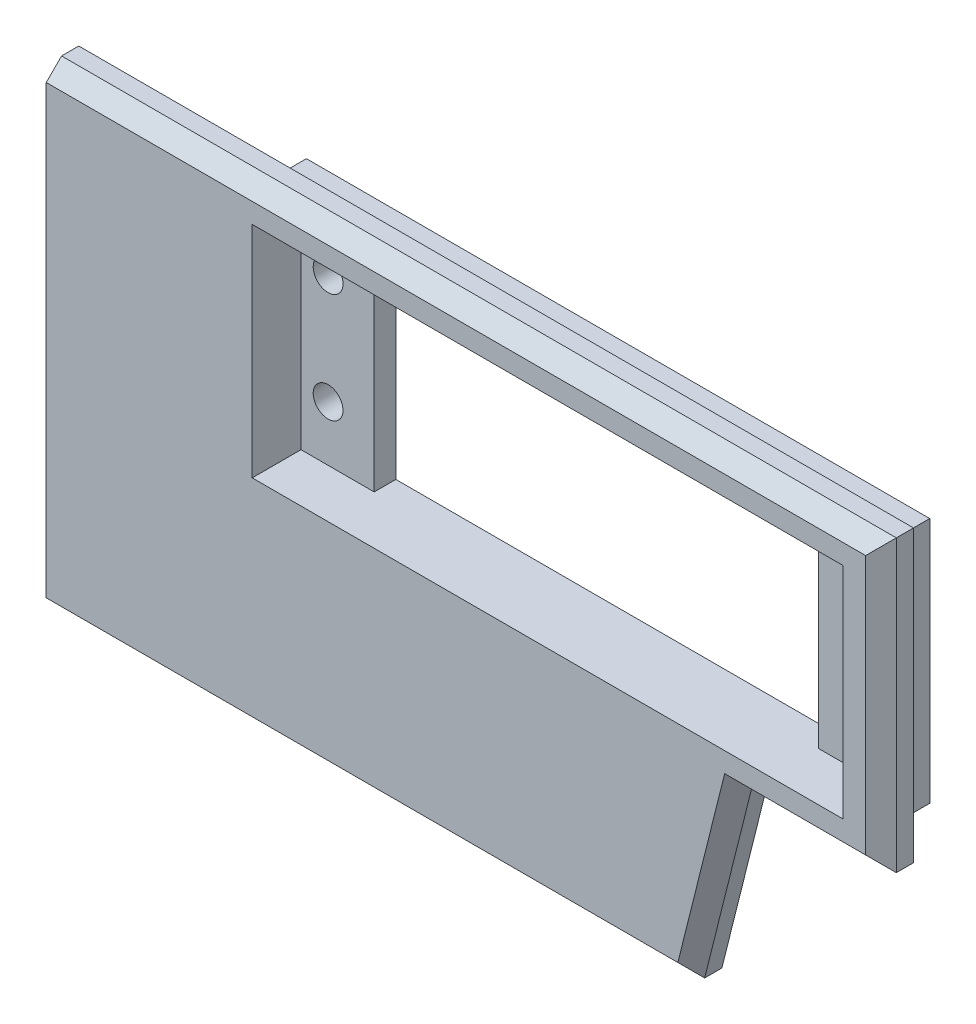
SolidWorks part; units mm, degrees
ref_plane "Front Plane" through (0, 0, 0) normal (0, 0, 1) x (1, 0, 0)
ref_plane "Top Plane" through (0, 0, 0) normal (0, 1, 0) x (1, 0, 0)
ref_plane "Right Plane" through (0, 0, 0) normal (1, 0, 0) x (0, 0, -1)
sketch "Sketch4" plane through (0, 0, 0) normal (0, 0, 1) x (1, 0, 0)
  line L0 (22.8744, -2.75) -> (36.233, -2.75)
  line L1 (36.233, -2.75) -> (36.233, 24)
  line L2 (36.233, 24) -> (-40.767, 24)
  line L3 (-40.767, 24) -> (-40.767, -20)
  line L4 (-40.767, -20) -> (18.556, -20)
  line L5 (18.556, -20) -> (22.8744, -2.75)
  line L10 (-42.767, -20) -> (18.556, -20) construction
  line L11 (-40.767, 18) -> (-40.767, -14.04) construction
  line L12 (36.233, -2.75) -> (36.233, 24) construction
  line L13 (36.233, 24) -> (-52.767, 24) construction
  line L14 (22.8744, -2.75) -> (36.233, -2.75) construction
extrude "Boss-Extrude1" add sketch "Sketch4" along normal blind 3
sketch "Sketch5" plane through (36.233, 0, 0) normal (1, 0, 0) x (0, 0, -1)
  line L0 (-1.5858, 24) -> (-3, 22.5858)
  line L1 (-3, 24) -> (0, 24) construction
  line L2 (-3, -2.75) -> (-3, 24) construction
  line L3 (-3, 22.5858) -> (-3, 24)
  line L4 (-3, 24) -> (-1.5858, 24)
  line L5 (-3, -18.5858) -> (-1.5858, -20)
  line L6 (-3, -20) -> (-3, -2.75) construction
  line L7 (-3, -20) -> (0, -20) construction
  line L8 (-1.5858, -20) -> (-3, -20)
  line L9 (-3, -20) -> (-3, -18.5858)
  line L10 (-3, 10.625) -> (0, 10.625) construction
  line L11 (0, -2.75) -> (0, 24) construction
  line L12 (-3, -1.3358) -> (-3, -2.75)
  line L13 (-3, -2.75) -> (-1.5858, -2.75)
  line L14 (-1.5858, -2.75) -> (-3, -1.3358)
  line M8 (0, 24) -> (-3, 24)
  line M9 (-3, 24) -> (-3, -2.75)
  line M10 (-3, -2.75) -> (0, -2.75)
  dimension "D1" = 2
  dimension "D2" = 2
extrude "Cut-Extrude1" cut sketch "Sketch5" against normal up to next contours L0 M8 M9 | L5 L8 L9 region at (36.233, 23.5286, 2.5286)
extrude "Cut-Extrude2" cut sketch "Sketch5<4>" against normal up to surface (13.0046 mm away) contours L14 M10 M9 region at (36.233, -2.2786, 2.5286) up to face at (20.3541, -12.8172, 1.5172)
sketch "Sketch5<4>" plane through (36.233, 0, 0) normal (1, 0, 0) x (0, 0, -1) same geometry as "Sketch5"
sketch "Sketch7" plane through (0, -2.75, 0) normal (0, -1, 0) x (1, 0, 0)
  line L0 (36.233, 1.5858) -> (34.8188, 3)
  line L4 (34.8188, 3) -> (36.233, 3)
  line L5 (36.233, 3) -> (36.233, 1.5858)
  line L6 (23.2284, 3) -> (36.233, 3) construction
  dimension "D1" = 2
extrude "Cut-Extrude3" cut sketch "Sketch7" against normal through all
sketch "Sketch8" plane through (0, -20, 0) normal (0, -1, 0) x (1, 0, 0)
  line L0 (17.1417, 3) -> (18.556, 3)
  line L2 (18.556, 3) -> (18.556, 1.5858)
  line L3 (18.556, 1.5858) -> (18.556, 0) construction
  line L4 (18.556, 1.5858) -> (17.1417, 3)
  line L5 (18.91, 3) -> (23.2284, 3) construction
  dimension "D1" = 2
extrude "Cut-Extrude4" cut sketch "Sketch8" along direction (0.2428, 0.9701, 0) on the side against the normal up to surface (17.7823 mm away) up to face at (29.2886, -2.0429, 2.2929)
sketch "Sketch10" plane through (0, 0, 0) normal (0, 0, -1) x (-1, 0, 0)
  line L35 (-34.233, 22) -> (40.767, 22)
  line L36 (40.767, -18) -> (-16.9949, -18)
  line L37 (-16.9949, -18) -> (-21.3133, -0.75)
  line L38 (-21.3133, -0.75) -> (-34.233, -0.75)
  line L39 (-34.233, -0.75) -> (-34.233, 22)
  line L40 (-34.233, 22) -> (40.767, 22)
  line L41 (40.767, -18) -> (-16.9949, -18)
  line L42 (-16.9949, -18) -> (-21.3133, -0.75)
  line L43 (-21.3133, -0.75) -> (-34.233, -0.75)
  line L44 (-34.233, -0.75) -> (-34.233, 22)
  dimension "D3" = 2
sketch "Sketch9" plane through (0, 0, 0) normal (0, 0, 1) x (1, 0, 0)
  line L0 (34.233, 22) -> (-40.767, 22) construction
  line L5 (36.233, -2.75) -> (36.233, 24) construction
  line L6 (36.233, 24) -> (36.233, -2.75) construction
  line L8 (-23.267, 22) -> (34.233, 22)
  line L9 (-23.267, 22) -> (-23.267, -0.75)
  line L10 (-23.267, -0.75) -> (34.233, -0.75)
  line L11 (34.233, 22) -> (34.233, -0.75)
  point P19 (36.233, 10.625)
  point P22 (34.233, 10.625)
  dimension "D3" = 2
  dimension "D4" = 57.5
extrude "Boss-Extrude2" add sketch "Sketch9" against normal blind 3.5 contours L10 L9 L8 | L8 L11 L10 region at (5.483, 10.625, 0)
sketch "Sketch13" plane through (0, 0, 3) normal (0, 0, 1) x (1, 0, 0)
  line L0 (-23.267, -0.75) -> (34.233, -0.75) construction
  line L4 (-21.767, 20.75) -> (32.733, 20.75)
  line L5 (-21.767, 20.75) -> (-21.767, 0.5)
  line L6 (-21.767, 0.5) -> (32.733, 0.5)
  line L7 (32.733, 20.75) -> (32.733, 0.5)
  line L8 (-21.767, 20.75) -> (32.733, 0.5) construction
  line L9 (-21.767, 0.5) -> (32.733, 20.75) construction
  line L14 (34.8188, 22.5858) -> (34.8188, -1.3358) construction
  point P0 (5.483, 10.625)
  point P9 (5.483, -0.75)
  point P10 (34.8188, 10.625)
  point P11 (5.483, 0.5)
  dimension "D1" = 54.5
  dimension "D2" = 20.25
extrude "Cut-Extrude6" cut sketch "Sketch13" against normal blind 4.5
sketch "Sketch14" plane through (0, 0, -1.5) normal (0, 0, 1) x (1, 0, 0)
  line L0 (32.733, 20.75) -> (-21.767, 20.75) construction
  line L1 (-15.017, 20.75) -> (25.983, 20.75)
  line L2 (-15.017, 20.75) -> (-15.017, 0.5)
  line L3 (-15.017, 0.5) -> (25.983, 0.5)
  line L4 (25.983, 20.75) -> (25.983, 0.5)
  line L5 (-15.017, 20.75) -> (25.983, 0.5) construction
  line L6 (-15.017, 0.5) -> (25.983, 20.75) construction
  line L7 (-21.767, 0.5) -> (32.733, 0.5) construction
  point P0 (5.483, 10.625)
  point P18 (5.483, 0.5)
  point P19 (5.483, 0.5)
  dimension "D1" = 41
extrude "Cut-Extrude7" cut sketch "Sketch14" against normal up to surface (2 mm away) up to face at (5.483, 10.625, -3.5)
sketch "Sketch15" plane through (0, 0, -1.5) normal (0, 0, 1) x (1, 0, 0)
  line L0 (-21.767, 10.625) -> (32.733, 10.625) construction
  line L1 (-21.767, 20.75) -> (-21.767, 0.5) construction
  line L2 (32.733, 0.5) -> (32.733, 20.75) construction
  line L3 (32.733, 20.75) -> (-21.767, 20.75) construction
  line L4 (5.483, 20.75) -> (5.483, 0.5) construction
  line L5 (-21.767, 0.5) -> (32.733, 0.5) construction
  line L7 (25.983, 19.85) -> (32.733, 19.85) construction
  line L8 (25.983, 19.85) -> (25.983, 1.4) construction
  line L9 (25.983, 1.4) -> (32.733, 1.4) construction
  line L10 (32.733, 19.85) -> (32.733, 1.4) construction
  line L11 (25.983, 19.85) -> (32.733, 1.4) construction
  line L12 (25.983, 1.4) -> (32.733, 19.85) construction
  line L15 (25.983, 0.5) -> (25.983, 20.75) construction
  circle A0 centre (30.233, 15.675) radius 1.375
  circle A1 centre (30.233, 5.575) radius 1.375
  circle A2 centre (-19.267, 5.575) radius 1.375
  circle A3 centre (-19.267, 15.675) radius 1.375
  point P20 (29.358, 10.625)
  dimension "D1" = 2.75
  dimension "D2" = 5.05
  dimension "D3" = 2.5
  dimension "D4" = 18.45
extrude "Cut-Extrude8" cut sketch "Sketch15" against normal up to next
sketch "Sketch16" plane through (0, 0, 0) normal (0, 0, -1) x (-1, 0, 0)
  line L1 (22.9598, -4) -> (40.767, -4)
  line L2 (22.9598, -4) -> (22.9598, -7)
  line L3 (22.9598, -7) -> (40.767, -7)
  line L4 (40.767, -4) -> (40.767, -7)
  line L5 (22.9598, -4) -> (40.767, -7) construction
  line L6 (22.9598, -7) -> (40.767, -4) construction
  line L7 (41.767, -18) -> (41.767, 7) construction
  line L8 (40.767, 24) -> (40.767, -20) construction
  point P0 (31.8634, -5.5)
  point P7 (41.767, -5.5)
  point P8 (40.767, -5.5)
  dimension "D1" = 3
  dimension "D2" = 17.8072
extrude "Cut-Extrude9" cut sketch "Sketch16" against normal offset from surface (1.5 mm away) 1.5 up to face at (5.483, 10.625, 3)
